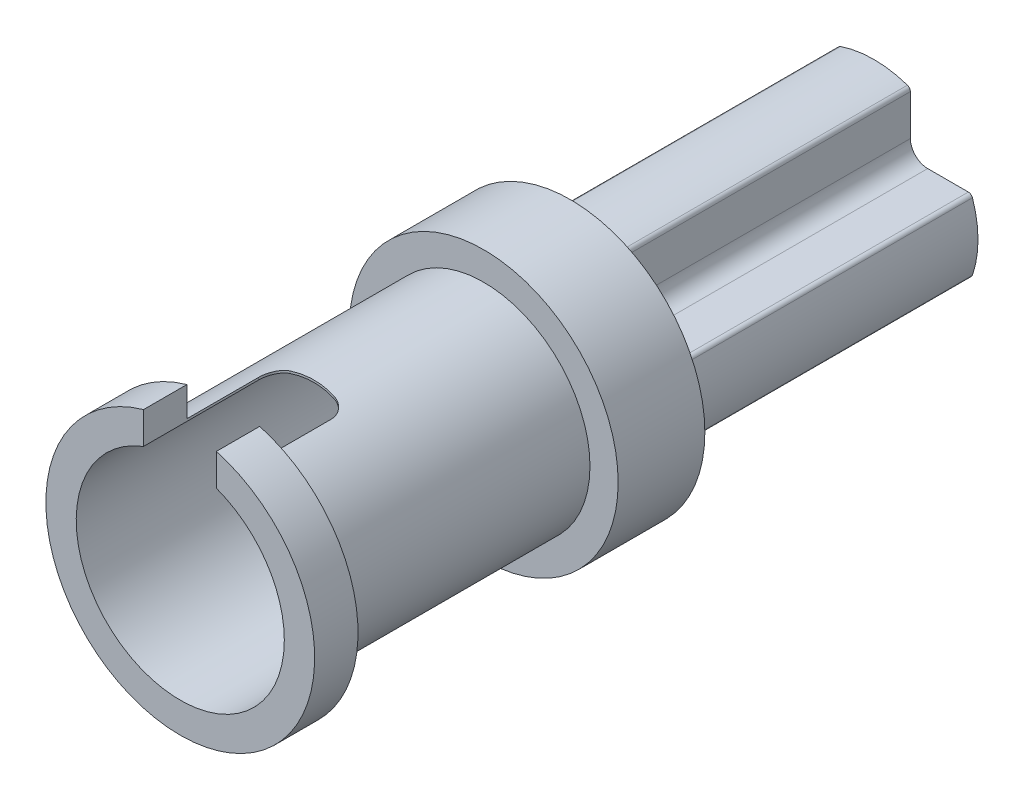
SolidWorks part; units mm, degrees
ref_plane "Front Plane" through (0, 0, 0) normal (0, 0, 1) x (1, 0, 0)
ref_plane "Top Plane" through (0, 0, 0) normal (0, 1, 0) x (1, 0, 0)
ref_plane "Right Plane" through (0, 0, 0) normal (1, 0, 0) x (0, 0, -1)
ref_plane "Plane1" through (0, 0, 8) normal (0, 0, 1) x (1, 0, 0)
ref_plane "Plane2" through (0, 0, 16) normal (0, 0, 1) x (1, 0, 0)
sketch "Sketch1" plane through (0, 0, 8) normal (0, 0, 1) x (1, 0, 0)
  circle A0 centre (0, 0) radius 3.1
  dimension "D1" = 6.2
extrude "Boss-Extrude1" add sketch "Sketch1" along normal blind 1 and the other way blind 1
sketch "Sketch2" plane through (0, 0, 7) normal (0, 0, -1) x (-1, 0, 0)
  line L0 (0.84, -0.84) -> (0.84, -2.2482)
  line L2 (-0.84, 2.2482) -> (-0.84, 0.84)
  line L4 (0.84, 2.2482) -> (0.84, 0.84)
  line L5 (-0.84, 2.2482) -> (0.84, -2.2482) construction
  line L6 (-0.84, -2.2482) -> (0.84, 2.2482) construction
  line L7 (-2.2482, 0.84) -> (-0.84, 0.84)
  line L9 (-2.2482, -0.84) -> (-0.84, -0.84)
  line L11 (-2.2482, 0.84) -> (2.2482, -0.84) construction
  line L12 (-2.2482, -0.84) -> (2.2482, 0.84) construction
  line L13 (0.84, -0.84) -> (2.2482, -0.84)
  line L14 (-0.84, -0.84) -> (-0.84, -2.2482)
  line L16 (0.84, 0.84) -> (2.2482, 0.84)
  arc A0 (-2.2482, 0.84) -> (-2.2482, -0.84) centre (0, 0) ccw
  arc A1 (0.84, 2.2482) -> (-0.84, 2.2482) centre (0, 0) ccw
  arc A2 (2.2482, -0.84) -> (2.2482, 0.84) centre (0, 0) ccw
  arc A3 (-0.84, -2.2482) -> (0.84, -2.2482) centre (0, 0) ccw
  dimension "D1" = 4.8
  dimension "D2" = 1.68
  dimension "D3" = 1.68
  dimension "D4" = 1.4082
extrude "Boss-Extrude2" add sketch "Sketch2" along normal blind 7
sketch "Sketch3" plane through (0, 0, 16) normal (0, 0, 1) x (1, 0, 0)
  circle A0 centre (0, 0) radius 3.1
  dimension "D1" = 6.2
extrude "Boss-Extrude3" add sketch "Sketch3" against normal blind 1 separate body
sketch "Sketch4" plane through (0, 0, 8) normal (0, 0, 1) x (1, 0, 0)
  circle A0 centre (0, 0) radius 2.45
  dimension "D1" = 4.9
extrude "Boss-Extrude4" add sketch "Sketch4" along normal blind 7
sketch "Sketch5" plane through (0, 0, 16) normal (0, 0, 1) x (1, 0, 0)
  circle A0 centre (0, 0) radius 2.4
  dimension "D1" = 4.8
extrude "Cut-Extrude1" cut sketch "Sketch5" against normal blind 7
ref_plane "Plane3" through (0, 5, 0) normal (0, 1, 0) x (1, 0, 0)
ref_axis "Axis2" through (3.41, 5, 16) along (-1, 0, 0)
sketch "Sketch7" plane through (0, 5, 0) normal (0, 1, 0) x (1, 0, 0)
  line L7 (-0.8479, -13.0251) -> (-0.8479, -18.9932)
  line L9 (0.8321, -13.0251) -> (0.8321, -18.9932)
  line L10 (-0.8479, -13.0251) -> (0.8321, -18.9932) construction
  line L11 (-0.8479, -18.9932) -> (0.8321, -13.0251) construction
  arc A1 (0.8321, -13.0251) -> (-0.8479, -13.0251) centre (-0.0079, -16.0092) ccw
  arc A2 (-0.8479, -18.9932) -> (0.8321, -18.9932) centre (-0.0079, -16.0092) ccw
  dimension "D2" = 6.2
  dimension "D1" = 5.9681
  dimension "D3" = 1.68
extrude "Cut-Extrude3" cut sketch "Sketch7" against normal blind 4
fillet "Fillet3" radius 0.4 1 edges at (0.8321, 2.2777, 13.0251)
fillet "Fillet4" radius 0.4 1 edges at (-0.8479, 2.2719, 13.0251)
fillet "Fillet5" radius 0.4 1 edges at (0.84, -0.84, 3.5)
fillet "Fillet6" radius 0.4 1 edges at (0.84, 0.84, 3.5)
fillet "Fillet7" radius 0.4 1 edges at (-0.84, 0.84, 3.5)
fillet "Fillet8" radius 0.4 1 edges at (-0.84, -0.84, 3.5)
fillet "Fillet9" radius 0.1 1 edges at (2.2482, 0.84, 3.5)
fillet "Fillet10" radius 0.1 1 edges at (2.2482, -0.84, 3.5)
fillet "Fillet11" radius 0.1 1 edges at (0.84, -2.2482, 3.5)
fillet "Fillet12" radius 0.1 1 edges at (-0.84, -2.2482, 3.5)
fillet "Fillet13" radius 0.1 1 edges at (-2.2482, -0.84, 3.5)
fillet "Fillet14" radius 0.1 1 edges at (-2.2482, 0.84, 3.5)
fillet "Fillet15" radius 0.1 1 edges at (0.84, 2.2482, 3.5)
fillet "Fillet16" radius 0.1 1 edges at (-0.84, 2.2482, 3.5)
